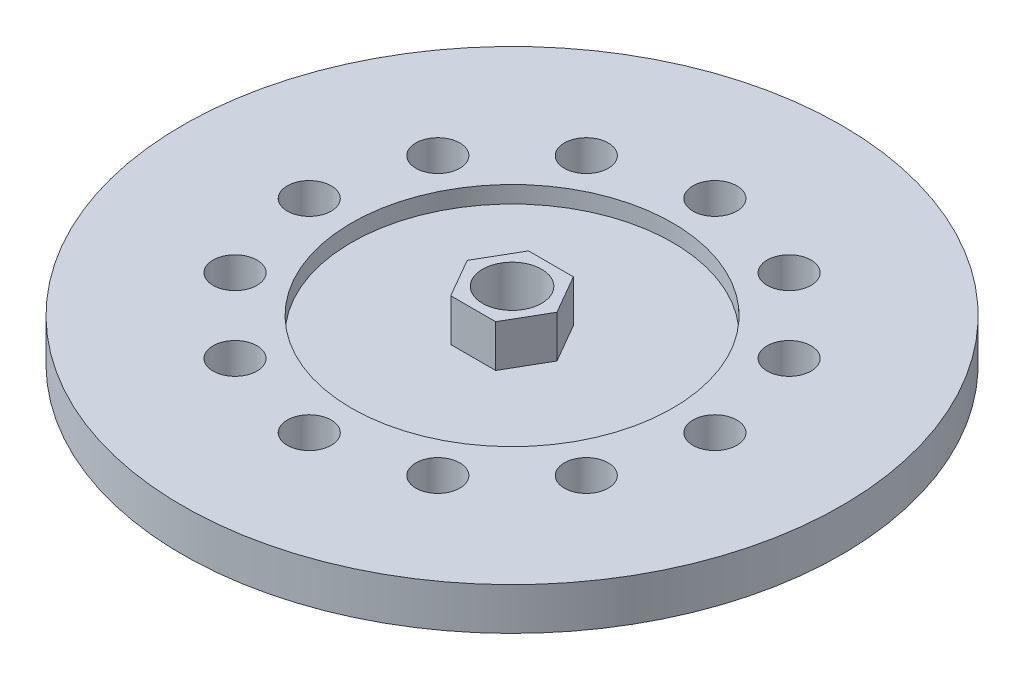
SolidWorks part; units mm, degrees
ref_plane "Front Plane" through (0, 0, 0) normal (0, 0, 1) x (1, 0, 0)
ref_plane "Top Plane" through (0, 0, 0) normal (0, 1, 0) x (1, 0, 0)
ref_plane "Right Plane" through (0, 0, 0) normal (1, 0, 0) x (0, 0, -1)
sketch "Sketch1" plane through (0, 0, 0) normal (0, 1, 0) x (1, 0, 0)
  circle A0 centre (0, 0) radius 49.53
  dimension "D1" = 99.06
extrude "Boss-Extrude1" add sketch "Sketch1" along normal blind 3.81
sketch "Sketch4" plane through (0, 3.81, 0) normal (0, 1, 0) x (1, 0, 0)
  line L0 (-3.3729, 5.842) -> (3.3729, 5.842)
  line L1 (3.3729, 5.842) -> (6.7458, 0)
  line L2 (6.7458, 0) -> (3.3729, -5.842)
  line L3 (3.3729, -5.842) -> (-3.3729, -5.842)
  line L4 (-3.3729, -5.842) -> (-6.7458, 0)
  line L5 (-6.7458, 0) -> (-3.3729, 5.842)
  circle A0 centre (0, 0) radius 4.445
  point P6 (0, 5.842)
  dimension "D3" = 8.89
  dimension "D1" = 120
  dimension "D2" = 11.684
extrude "Boss-Extrude2" add sketch "Sketch4" along normal blind 6.35 contours L5 L4 L3 L2 L1 L0 A0 region at (0, 3.81, -5.6635)
sketch "Sketch5" plane through (0, 3.81, 0) normal (0, 1, 0) x (1, 0, 0)
  circle A0 centre (0, 30.48) radius 3.302
  circle A1 centre (15.24, 26.3965) radius 3.302
  circle A2 centre (26.3965, 15.24) radius 3.302
  circle A3 centre (30.48, 0) radius 3.302
  circle A4 centre (26.3965, -15.24) radius 3.302
  circle A5 centre (15.24, -26.3965) radius 3.302
  circle A6 centre (0, -30.48) radius 3.302
  circle A7 centre (-15.24, -26.3965) radius 3.302
  circle A8 centre (-26.3965, -15.24) radius 3.302
  circle A9 centre (-30.48, 0) radius 3.302
  circle A10 centre (-26.3965, 15.24) radius 3.302
  circle A11 centre (-15.24, 26.3965) radius 3.302
  point P28 (0, 0)
  dimension "D2" = 6.604
  dimension "D1" = 30.48
extrude "Cut-Extrude1" cut sketch "Sketch5" against normal through all
sketch "Sketch6" plane through (0, 0, 0) normal (0, -1, 0) x (1, 0, 0)
  circle A0 centre (0, 0) radius 3.2639
  circle A1 centre (0, 0) radius 9.525
  dimension "D1" = 6.5278
  dimension "D2" = 19.05
extrude "Boss-Extrude3" add sketch "Sketch6" along normal blind 16.51 contours A1 A0 region at (-9.2556, 0, 0)
sketch "Sketch7" plane through (0, 0, 0) normal (0, -1, 0) x (1, 0, 0)
  line L2 (-3.2639, 0) -> (-3.2639, 20.32)
  line L3 (-3.2639, 20.32) -> (3.2639, 20.32)
  line L4 (3.2639, 0) -> (3.2639, 20.32)
  circle A0 centre (0, 0) radius 3.2639 construction
  arc A1 (3.2639, 0) -> (-3.2639, 0) centre (0, 0) ccw
  circle A2 centre (0, 0) radius 3.2639 construction
  dimension "D1" = 20.32
extrude "Boss-Extrude4" add sketch "Sketch7" along normal up to surface (16.51 mm away) up to face at (0, -16.51, -3.2639)
chamfer "Chamfer1" distance 10.16 angle 61 1 edges at (0, -16.51, 20.32) first distance on face at (0, -16.51, -3.2639)
pattern_circular "CirPattern1" count 4 over 360 about axis through (0, -16.51, 0) along (0, 1, 0) of "Boss-Extrude4", "Chamfer1" reverse direction yes
sketch "Sketch8" plane through (0, 3.81, 0) normal (0, 1, 0) x (1, 0, 0)
  circle A0 centre (0, 0) radius 49.53
  circle A1 centre (0, 0) radius 24.13
  circle A2 centre (0, 0) radius 49.53 construction
  circle A4 centre (0, 30.48) radius 3.302
  circle A5 centre (0, 30.48) radius 3.302 construction
  circle A6 centre (15.24, 26.3965) radius 3.302
  circle A7 centre (26.3965, 15.24) radius 3.302
  circle A8 centre (30.48, 0) radius 3.302
  circle A9 centre (26.3965, -15.24) radius 3.302
  circle A10 centre (15.24, -26.3965) radius 3.302
  circle A11 centre (0, -30.48) radius 3.302
  circle A12 centre (-15.24, -26.3965) radius 3.302
  circle A13 centre (-26.3965, -15.24) radius 3.302
  circle A14 centre (-30.48, 0) radius 3.302
  circle A15 centre (-26.3965, 15.24) radius 3.302
  circle A16 centre (-15.24, 26.3965) radius 3.302
  point P36 (0, 0)
  dimension "D1" = 25.4
  dimension "D2" = 12
extrude "Boss-Extrude5" add sketch "Sketch8" along normal blind 2.54
